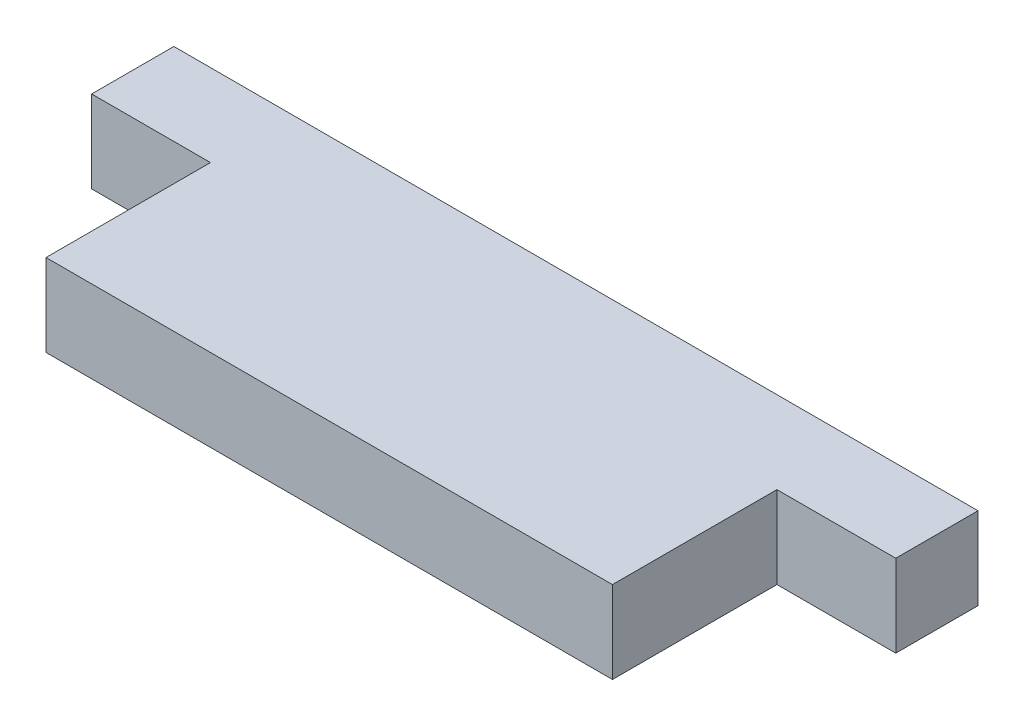
SolidWorks part; units mm, degrees
material "Beech"
ref_plane "Front Plane" through (0, 0, 0) normal (0, 0, 1) x (1, 0, 0)
ref_plane "Top Plane" through (0, 0, 0) normal (0, 1, 0) x (1, 0, 0)
ref_plane "Right Plane" through (0, 0, 0) normal (1, 0, 0) x (0, 0, -1)
sketch "Sketch1" plane through (0, 0, 0) normal (0, 1, 0) x (1, 0, 0)
  line L0 (0, 0) -> (0, 12.7)
  line L1 (0, 0) -> (43.74, 0)
  line L3 (43.74, 0) -> (43.74, 12.7)
  line L4 (-9.1751, 19.05) -> (52.9151, 19.05)
  line L5 (-9.1751, 19.05) -> (-9.1751, 12.7)
  line L6 (52.9151, 19.05) -> (52.9151, 12.7)
  line L7 (-9.1751, 12.7) -> (0, 12.7)
  line L8 (43.74, 12.7) -> (52.9151, 12.7)
  dimension "D1" = 12.7
  dimension "D2" = 43.74
  dimension "D3" = 6.35
  dimension "D4" = 9.1751
  dimension "D5" = 9.1751
extrude "Boss-Extrude1" add sketch "Sketch1" along normal blind 6.35
equation "\"MotorMountLegLength\"=.25in"
equation "\"GearOffset\"=.264907in"
equation "\"D4@Sketch1\"=\"TriggerRackOffset\"+.125in"
equation "\"D5@Sketch1\"=\"TriggerRackOffset\"+.125in"
equation "\"D2@Sketch1\" = \"CageLeftBottomEdge\" + \"CageRightBottomEdge\""
equation "\"CageLeftBottomEdge\"=22.11mm"
equation "\"CageLeftTopEdge\"=22.11mm"
equation "\"CageRightBottomEdge\"=21.63mm"
equation "\"CageRightTopEdge\"=21.63mm"
equation "\"CageHeight\"=86.04mm"
equation "\"CageLength\"=73.76mm"
equation "\"CageTopScrewClearance\"=10mm"
equation "\"CageBottomScrewClearance\"=25mm"
equation "\"CageLeftTopDepth\"= 11.65mm"
equation "\"CageLeftBottomDepth\"=11.11mm"
equation "\"CageLeftTopHeight\"=8.56175mm"
equation "\"CageLeftBottomHeight\"=16mm"
equation "\"CageRightTopDepth\"= 11.05mm"
equation "\"CageRightBottomDepth\"=10.58mm"
equation "\"CageRightTopHeight\"=9.6mm"
equation "\"CageRightBottomHeight\"=15.49mm"
equation "\"CageLeftTopChannelDepth\"=2.41908mm"
equation "\"CageLeftBottomChannelDepth\"=2.588mm"
equation "\"CageLeftChannelHeight\"=11.7mm"
equation "\"CageRightTopChannelDepth\"=2.32mm"
equation "\"CageRightBottomChannelDepth\"=2.318mm"
equation "\"CageRightChannelHeight\"=10mm"
equation "\"CageChanRelHeight\"=23.99mm"
equation "\"CageChanRelDepth\"=5.492mm"
equation "\"CageChamberRadius\"=16.261mm"
equation "\"CageScrewDiameter\"=4.8mm"
equation "\"CageSetScrewDiameter\"=3.5mm"
equation "\"CageAxleRadius\"=6.639mm"
equation "\"CageAxleKeyHeight\"=1.619mm"
equation "\"CageAxleKeyWidth\"=2.662mm"
equation "\"CageHoseWindowWidth\"=16.29mm"
equation "\"CageHoseWindowHeight\"=26.5mm"
equation "\"CageHoseWindow-Edge\"=8.89mm"
equation "\"CageScrew-VerticalEdge\"=5.0mm"
equation "\"CageScrew-HorizontalEdge\"=7.5mm"
equation "\"CageScrew-HoseCornerScrewEdge\"=4.45mm"
equation "\"CageAxle-BottomEdge\"=56.05mm"
equation "\"CageAxle-FrontEdge\"=46.03mm"
equation "\"CageBackSetScrew-Axle\"=40mm"
equation "\"CageFrontSetScrew-Axle\"=22mm"
equation "\"CageVelocityWindow-BackEdge\"=34.8mm"
equation "\"CageVelocityWindow-BottomEdge\"=27.55mm"
equation "\"CageVelocityWindowHeight\"=22.29mm"
equation "\"CageVelocityWindowWidth\"=12.61mm"
equation "\"TriggerSlot-BottomEdge\"=6.35mm"
equation "\"TriggerSlot-FrontEdge\"=15mm"
equation "\"TriggerSlotSize\"=6.7mm"
equation "\"TriggerRackOffset\"=.236224in"
equation "\"TriggerSlotSizeInt\"=.25in"
equation "\"TriggerSlotSpacing\"=.25in"
equation "\"TriggerMiniSlotWidth\"=3.5mm"
equation "\"TriggerRackWidth\"=6.5mm"
equation "\"TGMGearFaceDiameter\"=24.40mm"
equation "\"TGMCylinderLength\"=15.00mm"
equation "\"TGMScrewHole-Center\"=8.70mm"
equation "\"TGMScrewHoleDiameter\"=5.04mm"
equation "\"TGMCenterHoleDiameter\"=9.50mm"
equation "\"TGMShaftCollarSideLength\"=19.00mm"
equation "\"TGMShaftCollarDockingDepth\"=7.00mm"
equation "\"whitemotordepth\"=11.27mm"
equation "\"whitemotorbackdepth\"=3.845mm"
equation "\"whitemotoraxledepth\" = 3.5mm"
equation "\"whitemotoraxleoffset\"=11.4mm"
equation "\"whitemotorwidth\"=12.07mm"
equation "\"whitemotorheight\"=16.68mm"
equation "\"whitemotorcylinderlength\" =13.04mm"
equation "\"whitemotorcylinderradius\"=3.845mm"
equation "\"whitemotorcylinderoffset\"=2.35mm"
equation "\"whitemotorcutoutlength\"=1.88mm"
equation "\"whitemotorouterrad\"=5mm"
equation "\"whitemotorinnerrad\"=2.95mm"
equation "\"elasticracklength\"=2in"
equation "\"elasticrackpegsize\"=.25in"
equation "\"elasticrackpegbuffer\"=.125in"
equation "\"elasticrackpegspacing\"=1.76476378in"
equation "\"elasticbaybuffer\"=.25in"
equation "\"elasticdepth\"=.125in"
equation "\"elasticbaydepth\"=.75in"
equation "\"motormountwidth\"=12mm"
equation "\"motormountcornerfillet\"=3mm"
